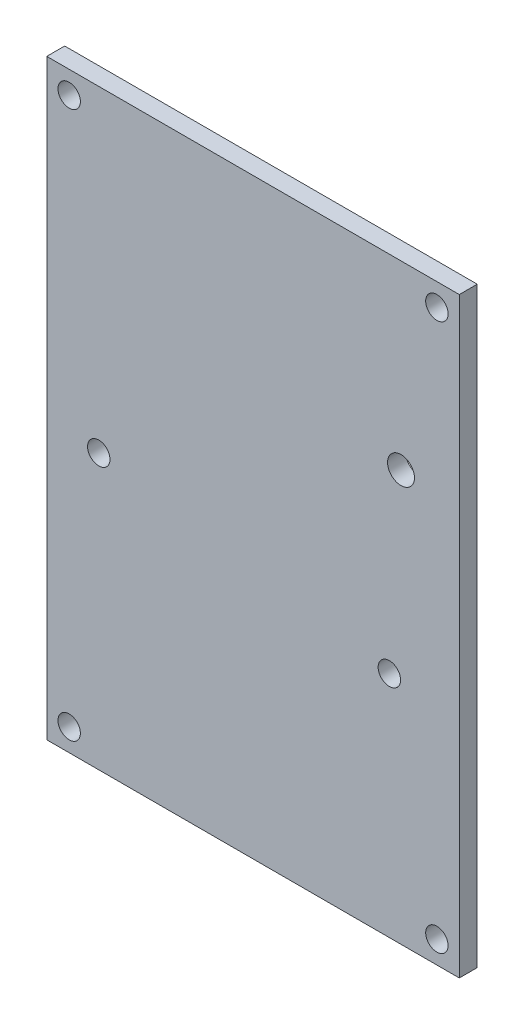
SolidWorks part; units mm, degrees
ref_plane "Front Plane" through (0, 0, 0) normal (0, 0, 1) x (1, 0, 0)
ref_plane "Top Plane" through (0, 0, 0) normal (0, 1, 0) x (1, 0, 0)
ref_plane "Right Plane" through (0, 0, 0) normal (1, 0, 0) x (0, 0, -1)
sketch "Sketch1" plane through (0, 0, 0) normal (0, 0, 1) x (1, 0, 0)
  line L1 (-23, -33) -> (23, -33)
  line L2 (-23, -33) -> (-23, 33)
  line L3 (-23, 33) -> (23, 33)
  line L4 (23, -33) -> (23, 33)
  line L5 (-23, -33) -> (23, 33) construction
  line L6 (-23, 33) -> (23, -33) construction
  point P0 (0, 0)
  dimension "D1" = 46
  dimension "D2" = 66
extrude "Boss-Extrude1" add sketch "Sketch1" along normal blind 2
hole_wizard "Ø2.5mm Dowel Hole1" positions "Sketch2" profile "Sketch3" hole size "Ø2.5" standard "DIN" end condition through all
sketch "Sketch2" plane through (0, 0, 2) normal (0, 0, 1) x (1, 0, 0)
  line L1 (-23, -33) -> (23, -33) construction
  line L2 (-23, 33) -> (-23, -33) construction
  line L3 (23, -33) -> (23, 33) construction
  point P0 (-20.5, 30.5)
  point P2 (20.5, 30.5)
  point P4 (20.5, -30.5)
  point P6 (-20.5, -30.5)
  point P8 (-17.2, -2.4)
  point P10 (15.2, -7.5)
  point P40 (0, 0)
  dimension "D1" = 41
  dimension "D2" = 41
  dimension "D3" = 2.5
  dimension "D4" = 2.5
  dimension "D5" = 63.5
  dimension "D6" = 30.6
  dimension "D7" = 5.8
  dimension "D8" = 7.8
  dimension "D10" = 25.5
sketch "Sketch3" plane through (-20.5, 30.5, 2) normal (1, 0, 0) x (0, -1, 0)
  line L0 (0, 0) -> (0, 2)
  line L1 (0, 2) -> (1.25, 2)
  line L2 (1.25, 2) -> (1.25, 0)
  line L5 (1.25, 0) -> (0, 0)
  line L11 (0, -6.35) -> (0, 107.95) construction
  dimension "Thru Hole Dia." = 2.5
  dimension "Thru Hole Depth" = 2
hole_wizard "Ø3.0mm Dowel Hole1" positions "Sketch4" profile "Sketch5" hole size "Ø3.0" standard "DIN" end condition through all
sketch "Sketch4" plane through (0, 0, 2) normal (0, 0, 1) x (1, 0, 0)
  line L0 (23, -33) -> (23, 33) construction
  line L1 (-23, -33) -> (23, -33) construction
  point P0 (16.5, 12.8)
  point P3 (0, 0)
  point P4 (0, 0)
  point P11 (14.5277, -26.6088)
  dimension "D1" = 6.5
  dimension "D2" = 45.8
sketch "Sketch5" plane through (16.5, 12.8, 2) normal (1, 0, 0) x (0, -1, 0)
  line L0 (0, 0) -> (0, 2)
  line L1 (0, 2) -> (1.5, 2)
  line L2 (1.5, 2) -> (1.5, 0)
  line L5 (1.5, 0) -> (0, 0)
  line L11 (0, -6.35) -> (0, 107.95) construction
  dimension "Thru Hole Dia." = 3
  dimension "Thru Hole Depth" = 2
